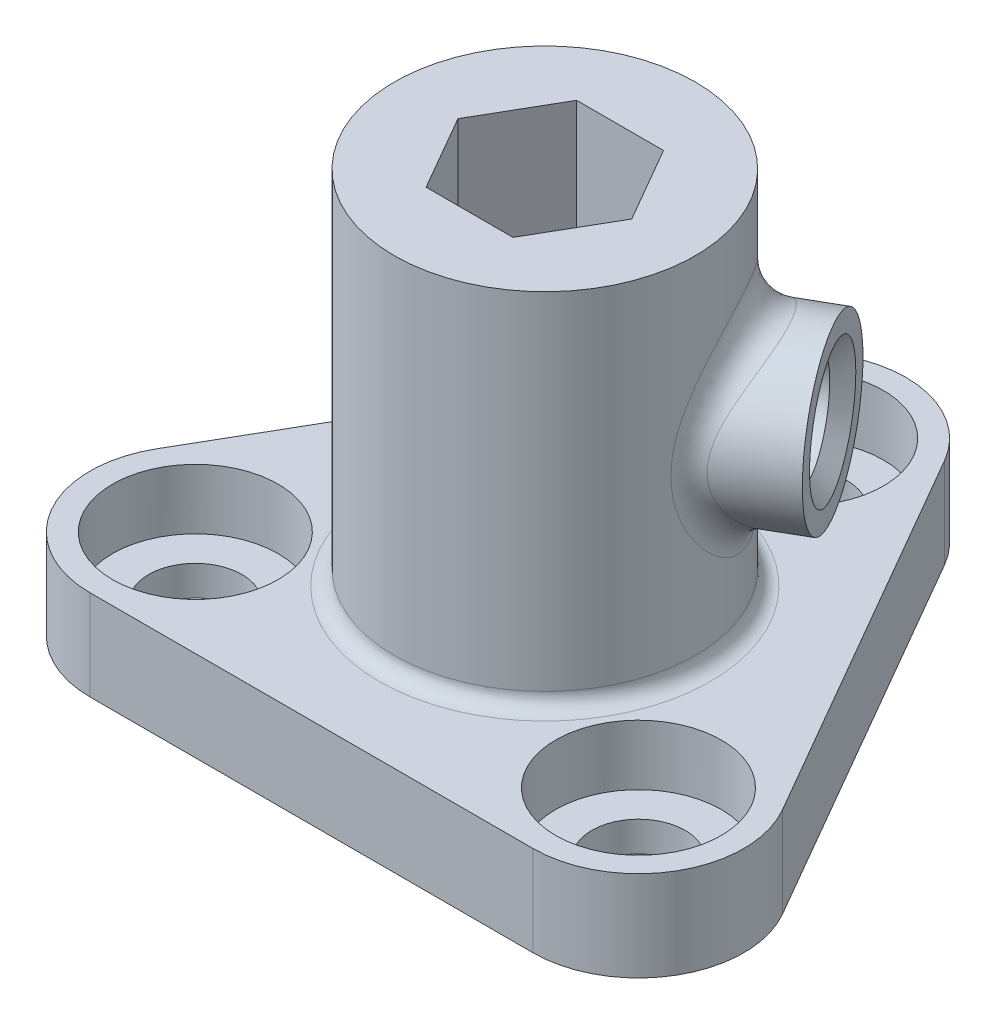
SolidWorks part; units mm, degrees
ref_plane "Front Plane" through (0, 0, 0) normal (0, 0, 1) x (1, 0, 0)
ref_plane "Top Plane" through (0, 0, 0) normal (0, 1, 0) x (1, 0, 0)
ref_plane "Right Plane" through (0, 0, 0) normal (1, 0, 0) x (0, 0, -1)
sketch "Sketch1" plane through (0, 0, 0) normal (1, 0, 0) x (0, 0, -1)
  line L1 (0, 0) -> (12, 0)
  line L2 (0, 0) -> (0, 5.3535)
  line L3 (5, 3) -> (12, 3)
  line L4 (12, 0) -> (12, 3)
  line L6 (0, 5.3535) -> (0, 15)
  line L7 (0, 15) -> (5, 15)
  line L8 (5, 3) -> (5, 15)
  dimension "D1" = 15
  dimension "6" = 5
  dimension "D3" = 3
  dimension "D4" = 7
revolve "Revolve1" add sketch "Sketch1" angle 360 about L6
sketch "Sketch4" plane through (0, 3, 0) normal (0, 1, 0) x (1, 0, 0)
  circle A0 centre (0, 8.5) radius 2.75
  circle A1 centre (7.3612, -4.25) radius 2.75
  circle A2 centre (-7.3612, -4.25) radius 2.75
  circle A6 centre (0, 0) radius 8.5 construction
  point P15 (0, 0)
  dimension "D2" = 17
  dimension "D3" = 5.5
  dimension "D1" = 3
extrude "Cut-Extrude4" cut sketch "Sketch4" against normal offset from surface (2 mm away) 1 up to face at (0, 0, -12)
sketch "Sketch5" plane through (0, 3, 0) normal (0, 1, 0) x (1, 0, 0)
  line L0 (-3.0311, 10.25) -> (-10.3923, -2.5)
  line L1 (-7.3612, -7.75) -> (7.3612, -7.75)
  line L2 (3.0311, 10.25) -> (10.3923, -2.5)
  arc A0 (3.0311, 10.25) -> (-3.0311, 10.25) centre (0, 8.5) ccw
  arc A1 (7.3612, -7.75) -> (10.3923, -2.5) centre (7.3612, -4.25) ccw
  arc A2 (-10.3923, -2.5) -> (-7.3612, -7.75) centre (-7.3612, -4.25) ccw
  circle A3 centre (0, 0) radius 12 construction
extrude "Cut-Extrude5" cut sketch "Sketch5" against normal through all flip side to cut
sketch "Sketch2" plane through (0, 15, 0) normal (0, 1, 0) x (1, 0, 0)
  line L0 (10.3923, -2.5) -> (3.0311, 10.25) construction
  line L1 (2.8868, 0) -> (1.4434, 2.5)
  line L2 (1.4434, 2.5) -> (-1.4434, 2.5)
  line L3 (-1.4434, 2.5) -> (-2.8868, 0)
  line L4 (-2.8868, 0) -> (-1.4434, -2.5)
  line L5 (-1.4434, -2.5) -> (1.4434, -2.5)
  line L6 (1.4434, -2.5) -> (2.8868, 0)
  circle A0 centre (0, 0) radius 2.5 construction
  dimension "D1" = 5
extrude "Cut-Extrude2" cut sketch "Sketch2" against normal offset from surface (16 mm away) 4 up to face at (0, 3, -5.75) offset beyond the face yes
ref_plane "Plane1" through (6.0622, 0, -3.5) normal (-0.866, 0, 0.5) x (0.5, 0, 0.866)
sketch "Sketch3" plane through (6.0622, 0, -3.5) normal (0.866, 0, -0.5) x (-0.5, 0, -0.866)
  line L0 (0, 15) -> (0, 3) construction
  line L1 (1.4434, 15) -> (-1.4434, 15) construction
  line L3 (5, 3) -> (-5, 3) construction
  circle A0 centre (0, 9) radius 2.75
  point P10 (0, 9)
  dimension "D1" = 5.5
extrude "Boss-Extrude1" add sketch "Sketch3" against normal up to next
sketch "Sketch6" plane through (6.0622, 0, -3.5) normal (0.866, 0, -0.5) x (-0.5, 0, -0.866)
  circle A0 centre (0, 9) radius 1.6
  dimension "D1" = 3.2
extrude "Cut-Extrude6" cut sketch "Sketch6" against normal up to next
fillet "Fillet1" radius 0.5 1 edges at (0, 3, -5)
chamfer "Chamfer1" distance 0.5 angle 45 1 edges at (5.2622, 9, -4.8856)
fillet "Fillet2" radius 1 1 edges at (4.9921, 8.766, 0.2817)
sketch "Sketch7" plane through (0, 3, 0) normal (0, 1, 0) x (1, 0, 0)
  circle A0 centre (0, 8.5) radius 1.55
  circle A1 centre (7.3612, -4.25) radius 1.55
  circle A2 centre (-7.3612, -4.25) radius 1.55
  dimension "D1" = 3.1
extrude "Cut-Extrude7" cut sketch "Sketch7" against normal through all
